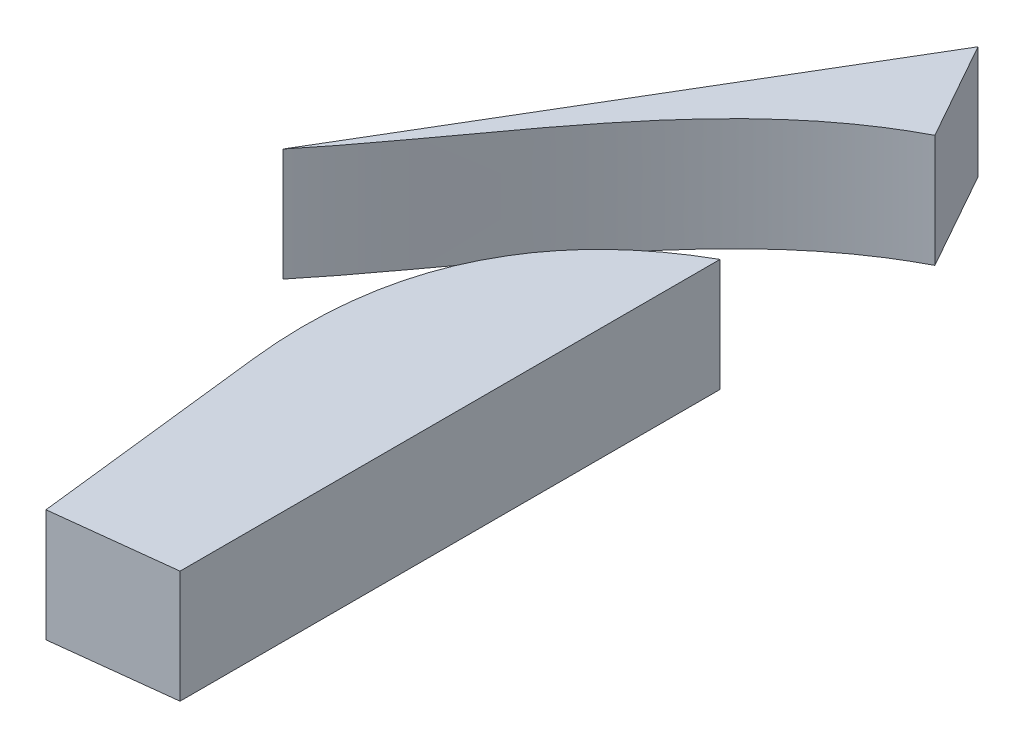
SolidWorks part; units mm, degrees
ref_plane "Front Plane" through (0, 0, 0) normal (0, 0, 1) x (1, 0, 0)
ref_plane "Top Plane" through (0, 0, 0) normal (0, 1, 0) x (1, 0, 0)
ref_plane "Right Plane" through (0, 0, 0) normal (1, 0, 0) x (0, 0, -1)
sketch "Sketch1" plane through (0, 0, 0) normal (0, 1, 0) x (1, 0, 0)
  line L0 (5.0859, -12.1132) -> (5.0859, -40.4808)
  line L1 (0.1928, 15.6756) -> (-22.7848, -23.0159)
  line L3 (5.0859, 6.9546) -> (0.1928, 15.6756)
  line L4 (-0.0254, -7.8387) -> (9.9731, -7.9617) [skipped]
  line L6 (5.0859, 6.9546) -> (5.0859, -12.1132) construction
  line L7 (-7.9798, -40.4808) -> (-5.5803, -61.2694)
  line L8 (-5.5803, -61.2694) -> (5.0859, -60.0382)
  line L9 (5.0859, -60.0382) -> (5.0859, -40.4808)
  circle A0 centre (0, 0) radius 7.8384 construction
  spline S0 degree 3 poles (-22.7848, -23.0159) (-14.1323, -12.5091) (-7.4839, 0.4388) (5.0859, 6.9546) knots 0 0 0 0 1 1 1 1
  spline S1 degree 3 poles (-7.9798, -40.4808) (-9.4842, -27.4476) (-5.1589, -17.9159) (5.0859, -12.1132) knots 0 0 0 0 1 1 1 1
  dimension "D1" = 45
  dimension "D2" = 10
extrude "Boss-Extrude1" add sketch "Sketch1" along normal blind 10
